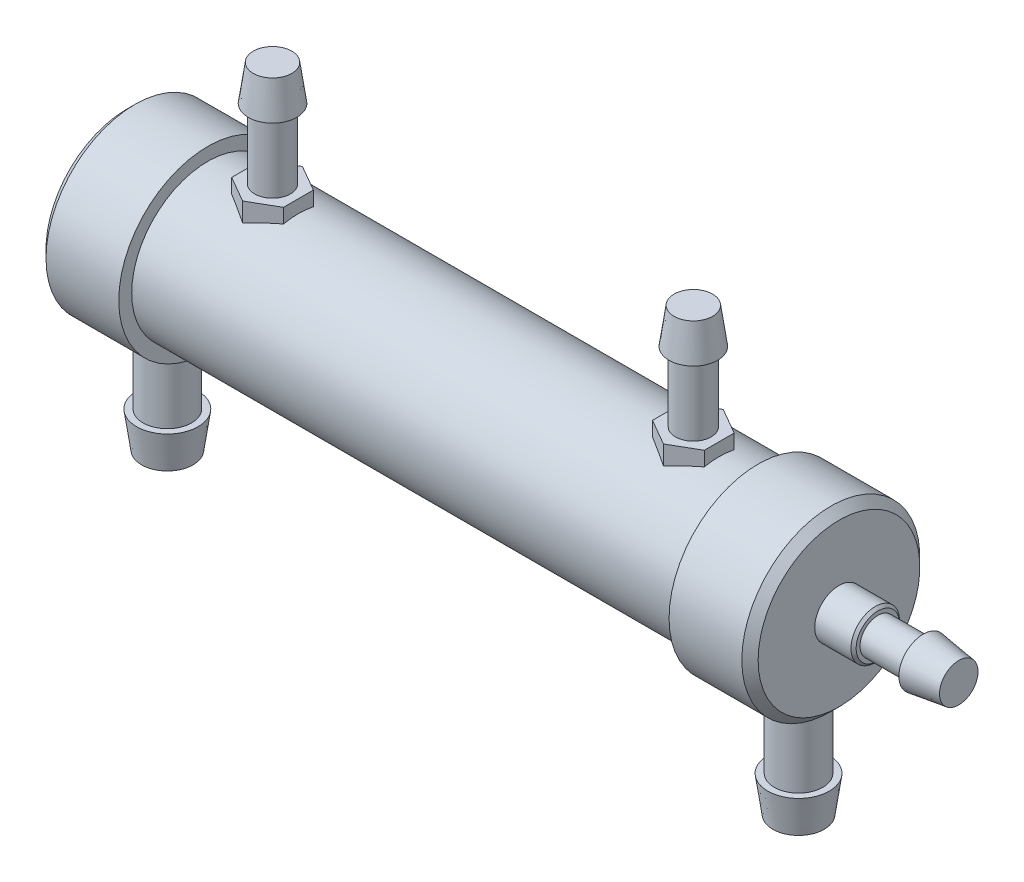
SolidWorks part; units mm, degrees
ref_plane "Front Plane" through (0, 0, 0) normal (0, 0, 1) x (1, 0, 0)
ref_plane "Top Plane" through (0, 0, 0) normal (0, 1, 0) x (1, 0, 0)
ref_plane "Right Plane" through (0, 0, 0) normal (1, 0, 0) x (0, 0, -1)
sketch "Sketch1" plane through (0, 0, 0) normal (0, 0, 1) x (1, 0, 0)
  line L0 (0, 0) -> (44839.0615, 0) construction
  line L1 (0, 0) -> (0, 17.4625)
  line L2 (0, 17.4625) -> (15.875, 17.4625)
  line L3 (15.875, 17.4625) -> (15.875, 14.9225)
  line L4 (15.875, 14.9225) -> (123.825, 14.9225)
  line L5 (123.825, 14.9225) -> (123.825, 17.4625)
  line L6 (123.825, 17.4625) -> (139.7, 17.4625)
  line L7 (139.7, 17.4625) -> (139.7, 4.7625)
  line L8 (163.195, 0) -> (0, 0)
  line L9 (139.7, 4.7625) -> (147.32, 4.7625)
  line L10 (147.32, 4.7625) -> (147.32, 3.4925)
  line L11 (147.32, 3.4925) -> (156.21, 3.4925)
  line L12 (156.21, 3.4925) -> (156.21, 4.7625)
  line L13 (156.21, 4.7625) -> (163.195, 3.7808)
  line L14 (163.195, 3.7808) -> (163.195, 0)
  point P13 (0, 0)
  point P18 (0, 0)
  point P19 (0, 0)
  point P20 (0, 0)
  point P21 (0, 0)
  dimension "D1" = 34.925
  dimension "D2" = 2.54
  dimension "D3" = 139.7
  dimension "D4" = 15.875
  dimension "D5" = 163.195
  dimension "D6" = 9.525
  dimension "D7" = 8.89
  dimension "D8" = 7.62
  dimension "D9" = 1.27
  dimension "D10" = 8
revolve "Revolve1" add sketch "Sketch1" angle 360 about L0
sketch "Sketch2" plane through (0, 0, 0) normal (0, 0, 1) x (1, 0, 0)
  line L0 (7.9375, -0.2613) -> (7.9375, -50000.2613) construction
  line L1 (0, 17.4625) -> (0, -17.4625) construction
  line L2 (12.7, -17.4625) -> (12.7, -31.115)
  line L3 (0, -17.4625) -> (15.875, -17.4625) construction
  line L4 (12.7, -31.115) -> (13.97, -31.115)
  line L5 (13.97, -31.115) -> (12.9883, -38.1)
  line L6 (12.9883, -38.1) -> (7.9375, -38.1)
  line L7 (7.9375, -38.1) -> (7.9375, -17.4625)
  line L8 (7.9375, -17.4625) -> (12.7, -17.4625)
  point P11 (0, 0)
  dimension "D1" = 7.9375
  dimension "D2" = 38.1
  dimension "D3" = 6.985
  dimension "D4" = 98
  dimension "D5" = 1.27
  dimension "D6" = 9.525
revolve "Revolve2" add sketch "Sketch2" angle 360 about L0
sketch "Sketch3" plane through (0, 0, 0) normal (0, 0, 1) x (1, 0, 0)
  line L0 (28.575, -0.8252) -> (28.575, 49999.1748) construction
  line L1 (25.0825, 14.9225) -> (25.0825, 31.115)
  line L2 (123.825, 14.9225) -> (15.875, 14.9225) construction
  line L3 (25.0825, 31.115) -> (23.8125, 31.115)
  line L4 (23.8125, 31.115) -> (24.7942, 38.1)
  line L5 (24.7942, 38.1) -> (28.575, 38.1)
  line L6 (28.575, 38.1) -> (28.575, 14.9225)
  line L7 (28.575, 14.9225) -> (25.0825, 14.9225)
  dimension "D1" = 28.575
  dimension "D2" = 9.525
  dimension "D3" = 8
  dimension "D4" = 6.985
  dimension "D5" = 1.27
  dimension "D6" = 38.1
revolve "Revolve3" add sketch "Sketch3" angle 360 about L0
ref_plane "Plane1" through (69.85, 0, 0) normal (-1, 0, 0) x (0, 0, 1)
mirror "Mirror4" about plane through (69.85, 0, 0) normal (-1, 0, 0) of bodies 102 103
sketch "Sketch4" plane through (0, 0, 0) normal (0, 1, 0) x (1, 0, 0)
  line L1 (33.655, -2.9329) -> (33.655, 2.9329)
  line L2 (33.655, 2.9329) -> (28.575, 5.8659)
  line L3 (28.575, 5.8659) -> (23.495, 2.9329)
  line L4 (23.495, 2.9329) -> (23.495, -2.9329)
  line L5 (23.495, -2.9329) -> (28.575, -5.8659)
  line L6 (28.575, -5.8659) -> (33.655, -2.9329)
  line L7 (111.125, -5.8659) -> (116.205, -2.9329)
  line L8 (116.205, -2.9329) -> (116.205, 2.9329)
  line L9 (116.205, 2.9329) -> (111.125, 5.8659)
  line L10 (111.125, 5.8659) -> (106.045, 2.9329)
  line L11 (106.045, 2.9329) -> (106.045, -2.9329)
  line L12 (106.045, -2.9329) -> (111.125, -5.8659)
  circle A0 centre (28.575, 0) radius 5.08 construction
  circle A1 centre (111.125, 0) radius 5.08 construction
  dimension "D1" = 10.16
extrude "Boss-Extrude1" add sketch "Sketch4" along normal blind 17.4625
chamfer "Chamfer1" distance 1.6002 angle 45 2 edges at (139.7, 0, 17.4625) (0, 0, 17.4625)
chamfer "Chamfer2" distance 0.508 angle 45 1 edges at (147.32, 0, 4.7625)
